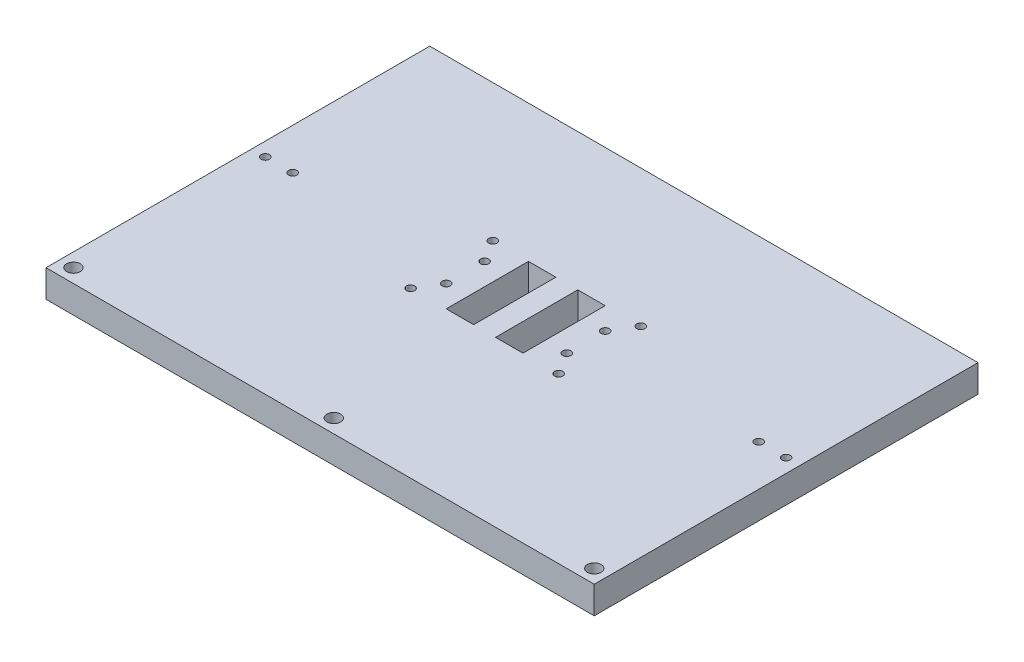
SolidWorks part; units mm, degrees
material "Perspex (TM) GS Acrylic Cast Sheet"
ref_plane "Front Plane" through (0, 0, 0) normal (0, 0, 1) x (1, 0, 0)
ref_plane "Top Plane" through (0, 0, 0) normal (0, 1, 0) x (1, 0, 0)
ref_plane "Right Plane" through (0, 0, 0) normal (1, 0, 0) x (0, 0, -1)
sketch "Sketch1" plane through (0, 0, 0) normal (0, 0, 1) x (1, 0, 0)
  line L1 (-100, 30) -> (100, 30)
  line L2 (-100, 30) -> (-100, -30)
  line L3 (-100, -30) -> (100, -30)
  line L4 (100, 30) -> (100, -30)
  line L5 (-100, 30) -> (100, -30) construction
  line L6 (-100, -30) -> (100, 30) construction
  point P0 (0, 0)
  dimension "D1" = 200
  dimension "D2" = 60
extrude "Boss-Extrude1" add sketch "Sketch1" along normal blind 10
sketch "Sketch2" plane through (0, 0, 0) normal (0, 0, -1) x (-1, 0, 0)
  line L0 (-100, -30) -> (-100, -20)
  line L1 (-100, -30) -> (-100, 30) construction
  line L2 (-100, -20) -> (100, -20)
  line L3 (100, 30) -> (100, -30) construction
  line L4 (100, -20) -> (100, -30)
  line L5 (100, -30) -> (-100, -30)
  dimension "D1" = 10
extrude "Boss-Extrude2" add sketch "Sketch2" along normal blind 130
sketch "Sketch3" plane through (0, 0, 10) normal (0, 0, 1) x (1, 0, 0)
  line L1 (0, -33) -> (0, 33) construction
  line L2 (-100, -30) -> (100, -30) construction
  circle A0 centre (0, 5) radius 15.5
  circle A1 centre (60, 5) radius 15.5
  circle A2 centre (-60, 5) radius 15.5
  dimension "D1" = 31
  dimension "D2" = 35
  dimension "D3" = 60
  dimension "D4" = 60
extrude "Cut-Extrude1" cut sketch "Sketch3" against normal blind 60
sketch "Sketch7" plane through (0, -20, 0) normal (0, 1, 0) x (1, 0, 0)
  line L0 (0, -5.5) -> (0, 5.5) construction
  line L1 (4, 80) -> (14, 80)
  line L2 (4, 80) -> (4, 50)
  line L3 (4, 50) -> (14, 50)
  line L4 (14, 80) -> (14, 50)
  line L5 (4, 80) -> (14, 50) construction
  line L6 (4, 50) -> (14, 80) construction
  line L8 (0, 115.3101) -> (0, 11.0931) construction
  line L9 (-4, 50) -> (-14, 80) construction
  line L10 (-4, 80) -> (-14, 50) construction
  line L11 (-14, 80) -> (-14, 50)
  line L12 (-4, 50) -> (-14, 50)
  line L13 (-4, 80) -> (-4, 50)
  line L14 (-4, 80) -> (-14, 80)
  line L15 (-5.5, 0) -> (5.5, 0) construction
  point P0 (9, 65)
  point P16 (-9, 65)
  dimension "D1" = 10
  dimension "D2" = 30
  dimension "D3" = 4
  dimension "D4" = 65
extrude "Cut-Extrude4" cut sketch "Sketch7" against normal blind 30
sketch "Sketch9" plane through (0, -20, 0) normal (0, 1, 0) x (1, 0, 0)
  line L0 (0, -5.5) -> (0, 5.5) construction
  line L1 (-27, 80) -> (27, 80) construction
  line L2 (-27, 80) -> (-27, 50) construction
  line L3 (-27, 50) -> (27, 50) construction
  line L4 (27, 80) -> (27, 50) construction
  line L5 (-27, 80) -> (27, 50) construction
  line L6 (-27, 50) -> (27, 80) construction
  line L7 (-5.5, 0) -> (5.5, 0) construction
  line L8 (-4, 50) -> (-4, 80) construction
  line L9 (-14, 80) -> (-14, 50) construction
  line L10 (-4, 65) -> (-14, 65) construction
  line L11 (0, 98.8977) -> (0, 27.4847) construction
  line L12 (100, -10) -> (-100, -10) construction
  line L13 (-100, -10) -> (-100, 0) construction
  line L14 (100, -10) -> (100, 0) construction
  line L15 (100, 130) -> (100, 0) construction
  circle A0 centre (-27, 80) radius 1.5
  circle A1 centre (27, 80) radius 1.5
  circle A2 centre (27, 50) radius 1.5
  circle A3 centre (-27, 50) radius 1.5
  circle A6 centre (-22, 72) radius 1.5
  circle A7 centre (-22, 58) radius 1.5
  circle A8 centre (22, 72) radius 1.5
  circle A9 centre (22, 58) radius 1.5
  circle A12 centre (0, -5) radius 2.5
  circle A13 centre (95, -5) radius 2.5
  circle A14 centre (-95, -5) radius 2.5
  circle A15 centre (95, 65) radius 1.5
  circle A16 centre (85, 65) radius 1.5
  circle A17 centre (-85, 65) radius 1.5
  circle A18 centre (-95, 65) radius 1.5
  point P0 (0, 65)
  dimension "D1" = 3
  dimension "D7" = 8
  dimension "D8" = 14
  dimension "D10" = 7
  dimension "D11" = 5
  dimension "D12" = 5
  dimension "D13" = 5
  dimension "D14" = 5
  dimension "D15" = 3
  dimension "D16" = 5
  dimension "D17" = 10
  dimension "D18" = 65
  dimension "D2" = 30
  dimension "D3" = 54
  dimension "D4" = 65
extrude "Cut-Extrude6" cut sketch "Sketch9" against normal blind 20
sketch "Sketch10" plane through (0, 0, 0) normal (1, 0, 0) x (0, 0, -1)
  line L1 (0, -20) -> (-33.7656, -20)
  line L2 (0, -20) -> (0, 42.6278)
  line L3 (0, 42.6278) -> (-33.7656, 42.6278)
  line L4 (-33.7656, -20) -> (-33.7656, 42.6278)
extrude "Cut-Extrude7" cut sketch "Sketch10" against normal mid plane 260
